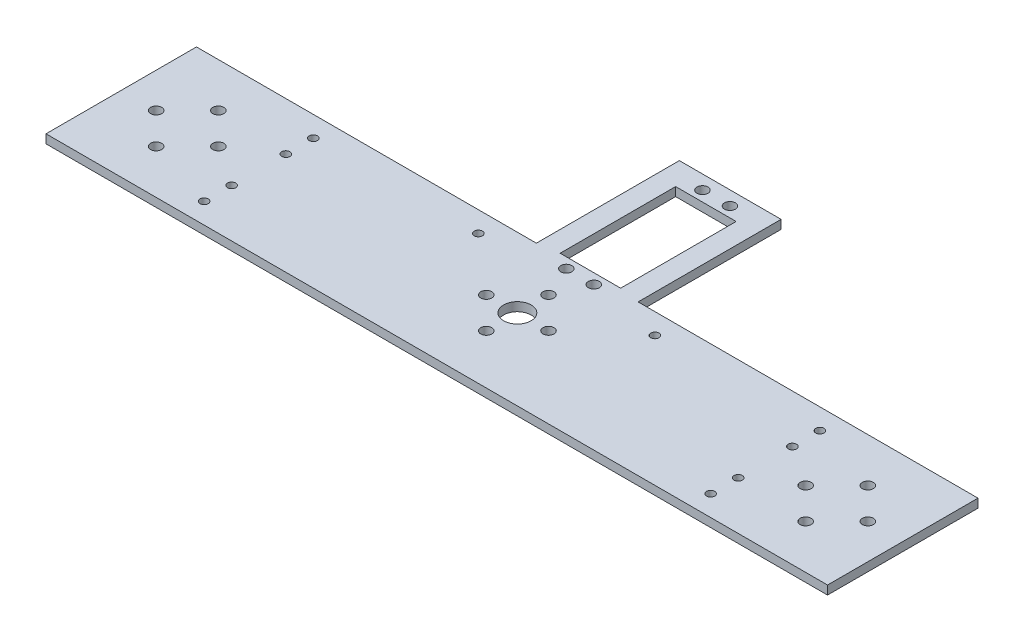
SolidWorks part; units mm, degrees
ref_plane "Front" through (0, 0, 0) normal (0, 0, 1) x (1, 0, 0)
ref_plane "Top" through (0, 0, 0) normal (0, 1, 0) x (1, 0, 0)
ref_plane "Right" through (0, 0, 0) normal (1, 0, 0) x (0, 0, -1)
sketch "Sketch1" plane through (0, 0, 0) normal (0, 1, 0) x (1, 0, 0)
  line L0 (0, -25.4) -> (284.2, -25.4)
  line L1 (0, 0) -> (284.2, 0)
  line L2 (0, 0) -> (0, -50.8)
  line L3 (0, -50.8) -> (284.2, -50.8)
  line L4 (284.2, 0) -> (284.2, -50.8)
  line L7 (115.2643, 0) -> (138.7357, 0)
  line L9 (142.1, -25.4) -> (142.1, 32.2)
  line L10 (142.1, 32.2) -> (142.1, 46.8974)
  line L11 (137.1, 46.8974) -> (147.1, 46.8974)
  line L12 (137.1, -2.6026) -> (147.1, -2.6026)
  line L13 (123.6, 0) -> (123.6, 52)
  line L14 (123.6, 52) -> (160.6, 52)
  line L15 (160.6, 52) -> (160.6, 0)
  line L16 (142.1, -2.6026) -> (142.1, 46.8974)
  line L17 (131.1, 22.1474) -> (153.1, 22.1474)
  line L18 (131.1, 1.1474) -> (131.1, 43.1474)
  line L19 (131.1, 1.1474) -> (153.1, 1.1474)
  line L20 (153.1, 1.1474) -> (153.1, 43.1474)
  line L21 (153.1, 43.1474) -> (131.1, 43.1474)
  line L22 (0, -50.8) -> (284.2, -50.8)
  line L23 (0, -50.8) -> (0, -54.7137)
  line L24 (284.2, -50.8) -> (284.2, -54.7137)
  line L25 (0, -54.7137) -> (284.2, -54.7137)
  circle A0 centre (142.1, -25.4) radius 11.3137
  circle A1 centre (142.1, -36.7137) radius 2
  circle A2 centre (153.4137, -25.4) radius 2
  circle A3 centre (142.1, -14.0863) radius 2
  circle A4 centre (130.7863, -25.4) radius 2
  circle A5 centre (142.1, -25.4) radius 5
  circle A6 centre (137.1, -2.6026) radius 2
  circle A7 centre (147.1, -2.6026) radius 2
  circle A8 centre (137.1, 46.8974) radius 2
  circle A9 centre (147.1, 46.8974) radius 2
  point P25 (142.1, 46.8974)
  point P28 (142.1, -2.6026)
  point P40 (142.1, 22.1474)
  point P43 (131.1, 22.1474)
  dimension "D3" = 57.6
  dimension "D8" = 37
  dimension "D13" = 18
  dimension "D14" = 22.6274
  dimension "D1" = 284.2
  dimension "D2" = 50.8
  dimension "D4" = 10
  dimension "D5" = 10
  dimension "D6" = 49.5
  dimension "D7" = 14.6974
  dimension "D9" = 18.5
  dimension "D10" = 22
  dimension "D11" = 42
  dimension "D12" = 52
extrude "Boss-Extrude1" add sketch "Sketch1" along normal blind 3.175 contours A4 L0 L2 L3 L4 A2 A0 A1 | A6 L9 L1 L2 L0 A4 A0 A3 | A7 L9 A3 A0 A2 L0 L4 L1 L7 | A9 L7 L1 L15 L14 L13 A8 | A5 L0 A4 A0 A1 A2 | A5 L0 A2 A0 A3 L9 | A5 L9 A3 A0 A4 L0 | L23 L25 L24 L3 region at (147.5378, 0, 19.9622) region at (142.1, 0, 30.8378) region at (136.6622, 0, 19.9622) region at (215.4169, 0, 12.4972) region at (156.6904, 0, 28.9803) region at (68.7831, 0, 12.4972) region at (142.1, 0, 52.7569) region at (140.4179, 0, -0.6382)
sketch "Sketch2" plane through (0, 0, 0) normal (0, -1, 0) x (1, 0, 0)
  line L0 (50, 54.7137) -> (50, 0)
  line L1 (0, 54.7137) -> (284.2, 54.7137) construction
  line L2 (0, 0) -> (123.6, 0) construction
  line L3 (50, 7.5) -> (137.5197, 7.5)
  line L4 (50, 47.2137) -> (153.3965, 47.2137)
  line L5 (0, 0) -> (0, 54.7137) construction
  line L6 (142.1, 47.2137) -> (142.1, 7.5)
  circle A0 centre (50, 47.2137) radius 1.5
  circle A1 centre (50, 7.5) radius 1.5
  circle A2 centre (110, 7.5) radius 1.5
  circle A3 centre (174.2, 7.5) radius 1.5
  circle A4 centre (234.2, 7.5) radius 1.5
  circle A5 centre (234.2, 47.2137) radius 1.5
  circle A6 centre (50, 37.2137) radius 1.5
  circle A7 centre (50, 17.5) radius 1.5
  circle A8 centre (234.2, 37.2137) radius 1.5
  circle A9 centre (234.2, 17.5) radius 1.5
  dimension "D2" = 7.5
  dimension "D4" = 60
  dimension "D5" = 10
  dimension "D1" = 50
  dimension "D3" = 7.5
  dimension "D6" = 10
extrude "Cut-Extrude1" cut sketch "Sketch2" against normal blind 10 contours A0 | A5 | A1 | A2 | A3 | A4 | A6 | A7 | A8 | A9
sketch "Sketch3" plane through (0, 0, 0) normal (0, -1, 0) x (1, 0, 0)
  line L0 (0, 27.3569) -> (24, 27.3569)
  line L1 (0, 0) -> (0, 54.7137) construction
  line L2 (142.1, 30.4) -> (142.1, 20.4)
  circle A0 centre (24, 27.3569) radius 11.3137
  circle A1 centre (24, 38.6706) radius 2
  circle A2 centre (12.6863, 27.3569) radius 2
  circle A3 centre (35.3137, 27.3569) radius 2
  circle A4 centre (24, 16.0431) radius 2
  circle A5 centre (142.1, 25.4) radius 5 construction
  circle A6 centre (260.2, 16.0431) radius 2
  circle A7 centre (271.5137, 27.3569) radius 2
  circle A8 centre (260.2, 38.6706) radius 2
  circle A9 centre (248.8863, 27.3569) radius 2
  dimension "D1" = 24
extrude "Cut-Extrude2" cut sketch "Sketch3" against normal blind 10 contours A2 | A1 | A3 | A4 | A9 | A8 | A7 | A6
